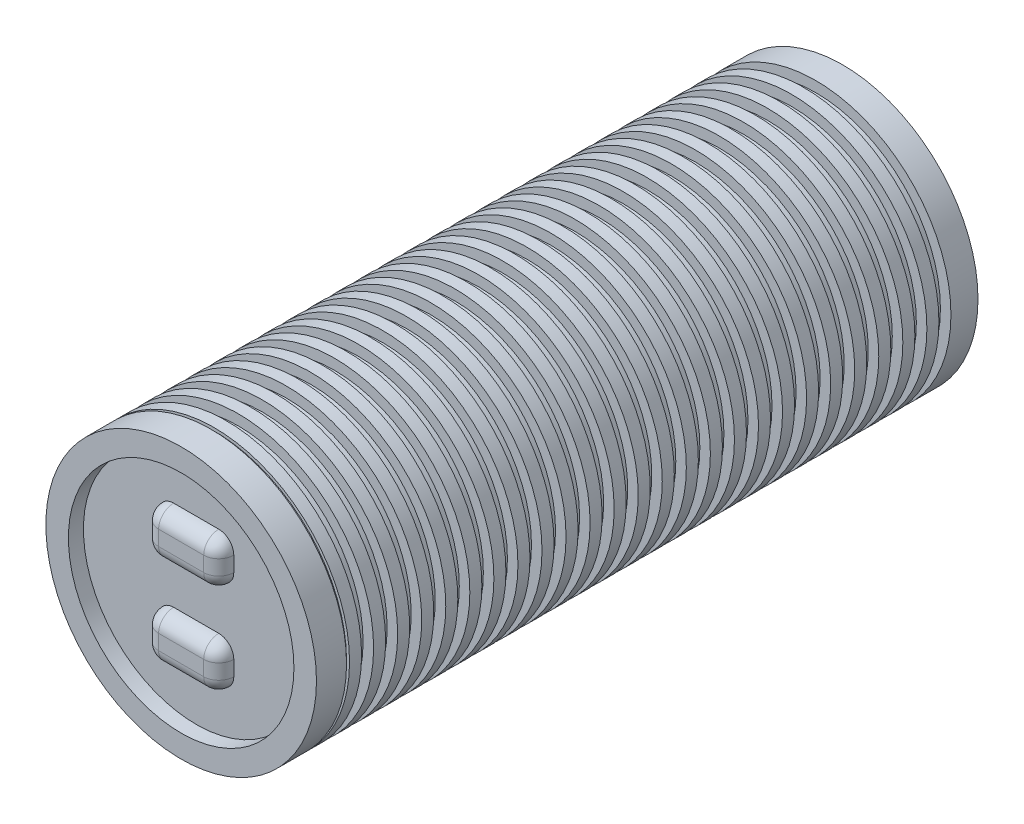
SolidWorks part; units mm, degrees
material "ABS"
ref_plane "Plan de face" through (0, 0, 0) normal (0, 0, 1) x (1, 0, 0)
ref_plane "Plan de dessus" through (0, 0, 0) normal (0, 1, 0) x (1, 0, 0)
ref_plane "Plan de droite" through (0, 0, 0) normal (1, 0, 0) x (0, 0, -1)
sketch "Esquisse1" plane through (0, 0, 0) normal (1, 0, 0) x (0, 0, -1)
  line L0 (3, 9) -> (3, 8.3)
  line L1 (1, 0) -> (44, 0)
  line L2 (0, 7.5) -> (0, 9)
  line L3 (0, 9) -> (2, 9)
  line L4 (44, 0) -> (44, 9)
  line L5 (0, 7.5) -> (1, 7.5)
  line L8 (1, 7.5) -> (1, 0)
  line L9 (3, 8.3) -> (3.8, 8.3)
  line L10 (3.8, 8.3) -> (3.8, 9)
  line L11 (4.6, 9) -> (4.6, 8.3)
  line L12 (7, 9) -> (7.8, 9)
  line L13 (2, 9) -> (2, 8.8)
  line L14 (2, 8.8) -> (2.2, 8.8)
  line L15 (2.2, 9) -> (2.2, 8.8)
  line L16 (4.6, 8.3) -> (5.4, 8.3)
  line L17 (5.4, 8.3) -> (5.4, 9)
  line L18 (6.2, 9) -> (6.2, 8.3)
  line L19 (6.2, 8.3) -> (7, 8.3)
  line L20 (7, 8.3) -> (7, 9)
  line L21 (7.8, 9) -> (7.8, 8.3)
  line L22 (7.8, 8.3) -> (8.6, 8.3)
  line L23 (8.6, 8.3) -> (8.6, 9)
  line L24 (9.4, 9) -> (9.4, 8.3)
  line L25 (9.4, 8.3) -> (10.2, 8.3)
  line L26 (10.2, 8.3) -> (10.2, 9)
  line L27 (11, 9) -> (11, 8.3)
  line L28 (11, 8.3) -> (11.8, 8.3)
  line L29 (11.8, 8.3) -> (11.8, 9)
  line L30 (12.6, 9) -> (12.6, 8.3)
  line L31 (12.6, 8.3) -> (13.4, 8.3)
  line L32 (13.4, 8.3) -> (13.4, 9)
  line L33 (14.2, 9) -> (14.2, 8.3)
  line L34 (14.2, 8.3) -> (15, 8.3)
  line L35 (15, 8.3) -> (15, 9)
  line L36 (15.8, 9) -> (15.8, 8.3)
  line L37 (15.8, 8.3) -> (16.6, 8.3)
  line L38 (16.6, 8.3) -> (16.6, 9)
  line L39 (17.4, 9) -> (17.4, 8.3)
  line L40 (17.4, 8.3) -> (18.2, 8.3)
  line L41 (18.2, 8.3) -> (18.2, 9)
  line L42 (19, 9) -> (19, 8.3)
  line L43 (19, 8.3) -> (19.8, 8.3)
  line L44 (19.8, 8.3) -> (19.8, 9)
  line L45 (20.6, 9) -> (20.6, 8.3)
  line L46 (20.6, 8.3) -> (21.4, 8.3)
  line L47 (21.4, 8.3) -> (21.4, 9)
  line L48 (22.2, 9) -> (22.2, 8.3)
  line L49 (22.2, 8.3) -> (23, 8.3)
  line L50 (23, 8.3) -> (23, 9)
  line L51 (23.8, 9) -> (23.8, 8.3)
  line L52 (23.8, 8.3) -> (24.6, 8.3)
  line L53 (24.6, 8.3) -> (24.6, 9)
  line L54 (25.4, 9) -> (25.4, 8.3)
  line L55 (25.4, 8.3) -> (26.2, 8.3)
  line L56 (26.2, 8.3) -> (26.2, 9)
  line L57 (27, 9) -> (27, 8.3)
  line L58 (27, 8.3) -> (27.8, 8.3)
  line L59 (27.8, 8.3) -> (27.8, 9)
  line L60 (28.6, 9) -> (28.6, 8.3)
  line L61 (28.6, 8.3) -> (29.4, 8.3)
  line L62 (29.4, 8.3) -> (29.4, 9)
  line L63 (30.2, 9) -> (30.2, 8.3)
  line L64 (30.2, 8.3) -> (31, 8.3)
  line L65 (31, 8.3) -> (31, 9)
  line L66 (31.8, 9) -> (31.8, 8.3)
  line L67 (31.8, 8.3) -> (32.6, 8.3)
  line L68 (32.6, 8.3) -> (32.6, 9)
  line L69 (33.4, 9) -> (33.4, 8.3)
  line L70 (33.4, 8.3) -> (34.2, 8.3)
  line L71 (34.2, 8.3) -> (34.2, 9)
  line L72 (35, 9) -> (35, 8.3)
  line L73 (35, 8.3) -> (35.8, 8.3)
  line L74 (35.8, 8.3) -> (35.8, 9)
  line L75 (36.6, 9) -> (36.6, 8.3)
  line L76 (36.6, 8.3) -> (37.4, 8.3)
  line L77 (37.4, 8.3) -> (37.4, 9)
  line L78 (38.2, 9) -> (38.2, 8.3)
  line L79 (38.2, 8.3) -> (39, 8.3)
  line L80 (39, 8.3) -> (39, 9)
  line L81 (39.8, 9) -> (39.8, 8.3)
  line L82 (39.8, 8.3) -> (40.6, 8.3)
  line L83 (40.6, 8.3) -> (40.6, 9)
  line L84 (41.4, 9) -> (41.4, 8.3)
  line L85 (41.4, 8.3) -> (42.2, 8.3)
  line L86 (42.2, 8.3) -> (42.2, 9)
  line L87 (5.4, 9) -> (6.2, 9)
  line L88 (3.8, 9) -> (4.6, 9)
  line L89 (2.2, 9) -> (3, 9)
  line L90 (8.6, 9) -> (9.4, 9)
  line L91 (10.2, 9) -> (11, 9)
  line L92 (11.8, 9) -> (12.6, 9)
  line L93 (13.4, 9) -> (14.2, 9)
  line L94 (15, 9) -> (15.8, 9)
  line L95 (16.6, 9) -> (17.4, 9)
  line L96 (18.2, 9) -> (19, 9)
  line L97 (19.8, 9) -> (20.6, 9)
  line L98 (21.4, 9) -> (22.2, 9)
  line L99 (23, 9) -> (23.8, 9)
  line L100 (24.6, 9) -> (25.4, 9)
  line L101 (26.2, 9) -> (27, 9)
  line L102 (37.4, 9) -> (38.2, 9)
  line L103 (35.8, 9) -> (36.6, 9)
  line L104 (34.2, 9) -> (35, 9)
  line L105 (32.6, 9) -> (33.4, 9)
  line L106 (27.8, 9) -> (28.6, 9)
  line L107 (29.4, 9) -> (30.2, 9)
  line L108 (31, 9) -> (31.8, 9)
  line L109 (39, 9) -> (39.8, 9)
  line L110 (40.6, 9) -> (41.4, 9)
  line L111 (42.2, 9) -> (44, 9)
  dimension "D1" = 0.8
  dimension "D2" = 0.7
  dimension "D3" = 0.2
  dimension "D4" = 0.2
  dimension "D5" = 1
  dimension "D6" = 2
  dimension "D7" = 0.8
  dimension "D8" = 9
  dimension "D9" = 44
  dimension "D11" = 7.5
  dimension "D10" = 25
revolve "Révolution1" add sketch "Esquisse1" angle 360 about L1
sketch "Esquisse2" plane through (0, 0, -1) normal (0, 0, 1) x (1, 0, 0)
  line L1 (-1.5, 4.5) -> (1.5, 4.5)
  line L2 (-2.5, 3.5) -> (-2.5, 2.5)
  line L3 (-1.5, 1.5) -> (1.5, 1.5)
  line L4 (2.5, 3.5) -> (2.5, 2.5)
  line L5 (1.5, -1.5) -> (-1.5, -1.5)
  line L6 (2.5, -2.5) -> (2.5, -3.5)
  line L7 (1.5, -4.5) -> (-1.5, -4.5)
  line L8 (-2.5, -2.5) -> (-2.5, -3.5)
  arc A0 (1.5, 4.5) -> (2.5, 3.5) centre (1.5, 3.5) cw
  arc A1 (1.5, 1.5) -> (2.5, 2.5) centre (1.5, 2.5) ccw
  arc A2 (1.5, -1.5) -> (2.5, -2.5) centre (1.5, -2.5) cw
  arc A3 (2.5, -3.5) -> (1.5, -4.5) centre (1.5, -3.5) cw
  arc A4 (-1.5, -4.5) -> (-2.5, -3.5) centre (-1.5, -3.5) cw
  arc A5 (-1.5, -1.5) -> (-2.5, -2.5) centre (-1.5, -2.5) ccw
  arc A6 (-2.5, 2.5) -> (-1.5, 1.5) centre (-1.5, 2.5) ccw
  arc A7 (-1.5, 4.5) -> (-2.5, 3.5) centre (-1.5, 3.5) ccw
  dimension "D8" = 1
  dimension "D1" = 3
  dimension "D2" = 5
  dimension "D3" = 5
  dimension "D4" = 3
  dimension "D5" = 1.5
  dimension "D6" = 1.5
  dimension "D7" = 2.5
extrude "Boss.-Extru.1" add sketch "Esquisse2" along normal blind 1
fillet "Congé1" radius 1 16 edges at (2.5, -3, 0) (2.2071, -4.2071, 0) (0, -4.5, 0) (-2.2071, -4.2071, 0) (-2.5, -3, 0) (-2.2071, -1.7929, 0) (0, -1.5, 0) (2.2071, -1.7929, 0) (2.5, 3, 0) (2.2071, 1.7929, 0) (0, 1.5, 0) (-2.2071, 1.7929, 0) (-2.5, 3, 0) (-2.2071, 4.2071, 0) (0, 4.5, 0) (2.2071, 4.2071, 0)
